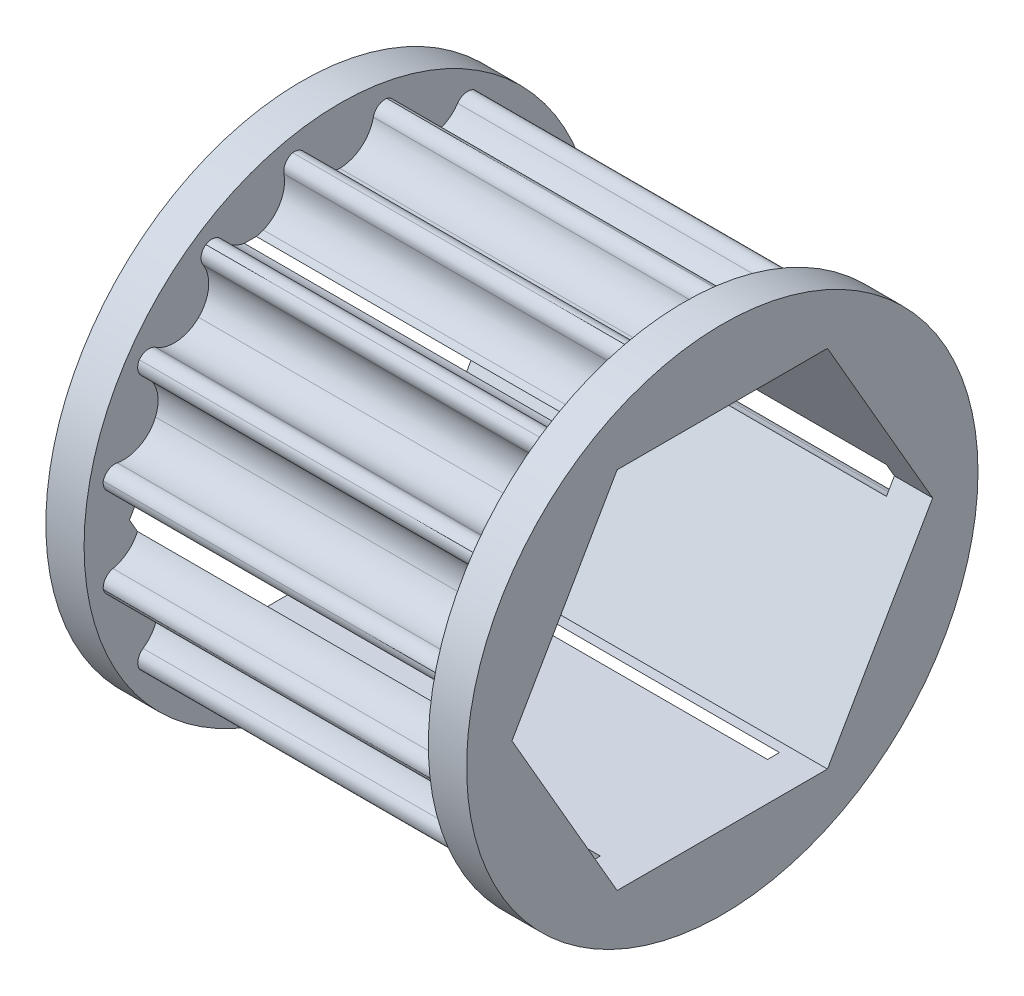
SolidWorks part; units mm, degrees
ref_plane "Front" through (0, 0, 0) normal (0, 0, 1) x (1, 0, 0)
ref_plane "Top" through (0, 0, 0) normal (0, 1, 0) x (1, 0, 0)
ref_plane "Right" through (0, 0, 0) normal (1, 0, 0) x (0, 0, -1)
sketch "Sketch1" plane through (0, 0, 0) normal (0, 0, 1) x (1, 0, 0)
  line L0 (5.5, 0) -> (-5.5, 0) construction
  line L1 (5.5, 3.175) -> (-5.5, 3.175)
  line L2 (5.5, 3.175) -> (5.5, 6.685)
  line L3 (5.5, 6.685) -> (-5.5, 6.685)
  line L4 (-5.5, 3.175) -> (-5.5, 6.685)
  point P4 (0, 3.175)
  dimension "D1" = 11
  dimension "D2" = 6.35
  dimension "D3" = 13.37
revolve "Revolve1" add sketch "Sketch1" angle 360 about L0
sketch "Sketch2" plane through (5.5, 0, 0) normal (1, 0, 0) x (0, 0, -1)
  line L0 (0, 0) -> (-2.9422, 7.089) construction
  line L1 (0, 0) -> (0, 7.6753) construction
  line L2 (-2.9422, 7.089) -> (0, 7.6753) construction
  line L3 (-1.4611, 5.823) -> (-1.5214, 6.1258)
  line L4 (-1.5214, 6.1258) -> (-0.943, 6.2411)
  line L5 (-0.943, 6.2411) -> (-0.8826, 5.9383)
  line L6 (-1.9987, 4.8159) -> (-2.6129, 6.2957)
  line L7 (-2.6129, 6.2957) -> (0, 6.8164)
  line L8 (0, 6.8164) -> (0, 5.2142)
  line L9 (-1.4611, 5.823) -> (-0.8826, 5.9383) construction
  arc A0 (-1.9987, 4.8159) -> (-1.4611, 5.823) centre (-2.3437, 5.6471) ccw
  circle A2 centre (0, 0) radius 6.685 construction
  arc A3 (-0.8826, 5.9383) -> (0, 5.2142) centre (0, 6.1142) ccw
  circle A6 centre (0, 0) radius 6.305 construction
  dimension "D1" = 0.3087
  dimension "D2" = 13.37
  dimension "D5" = 0.9
  dimension "D6" = 12.61
  dimension "D3" = 11.27
  dimension "D4" = 3
  dimension "D7" = 11.27
extrude "Cut-Extrude3" cut sketch "Sketch2" against normal offset from surface (9 mm away) 1 from offset 1 up to face at (-5.5, 0, -3.175) offset against normal yes
fillet "Fillet1" radius 0.3175 2 edges at (0, 6.2411, 0.943) (0, 6.1258, 1.5214)
pattern_circular "CirPattern1" count 16 over 360 about axis through (5.5, 0, 0) along (1, 0, 0) of "Fillet1", "Cut-Extrude3"
sketch "Sketch3" plane through (-5.5, 0, 0) normal (-1, 0, 0) x (0, 0, 1)
  line L1 (5.4993, 0) -> (2.7496, 4.7625)
  line L2 (2.7496, 4.7625) -> (-2.7496, 4.7625)
  line L3 (-2.7496, 4.7625) -> (-5.4993, 0)
  line L4 (-5.4993, 0) -> (-2.7496, -4.7625)
  line L5 (-2.7496, -4.7625) -> (2.7496, -4.7625)
  line L6 (2.7496, -4.7625) -> (5.4993, 0)
  circle A0 centre (0, 0) radius 4.7625 construction
  dimension "D1" = 9.525
extrude "Cut-Extrude4" cut sketch "Sketch3" against normal through all
